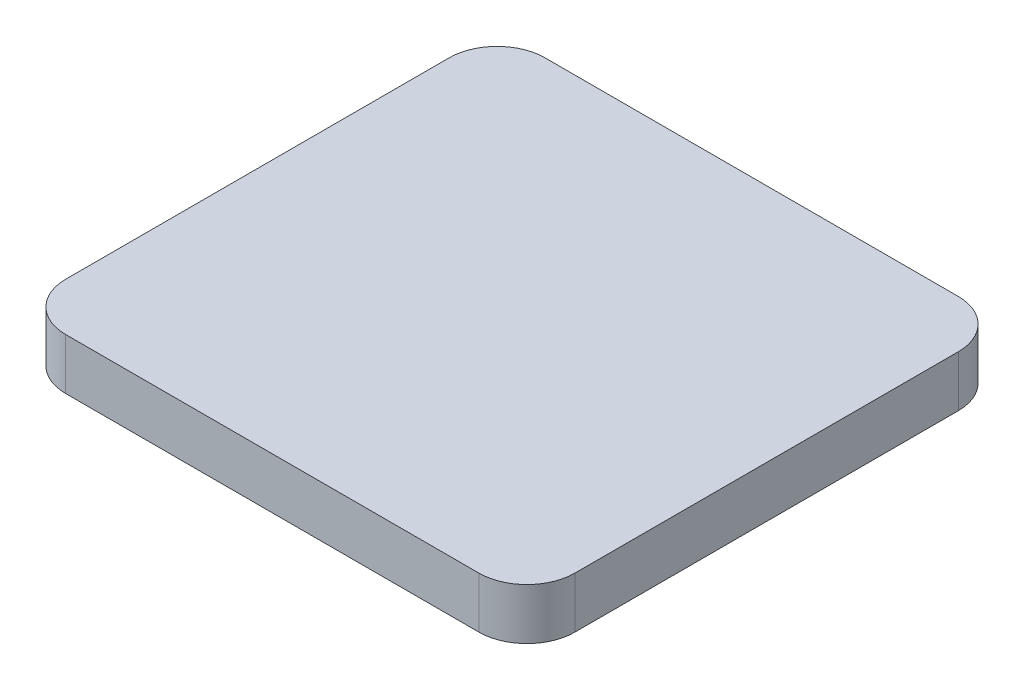
SolidWorks part; units mm, degrees
ref_plane "Front Plane" through (0, 0, 0) normal (0, 0, 1) x (1, 0, 0)
ref_plane "Top Plane" through (0, 0, 0) normal (0, 1, 0) x (1, 0, 0)
ref_plane "Right Plane" through (0, 0, 0) normal (1, 0, 0) x (0, 0, -1)
sketch "Sketch1" plane through (0, 0, 0) normal (0, 1, 0) x (1, 0, 0)
  line L0 (-21.9, 20.5) -> (-21.9, 22.5) construction
  line L1 (19.4, 20.5) -> (-19.4, 20.5)
  line L2 (21.9, 18) -> (21.9, -18)
  line L3 (19.4, -20.5) -> (-19.4, -20.5)
  line L4 (-21.9, 18) -> (-21.9, -18)
  line L5 (21.9, 20.5) -> (-21.9, -20.5) construction
  line L6 (21.9, -20.5) -> (-21.9, 20.5) construction
  line L7 (23.9, -22.5) -> (-23.9, -22.5)
  line L8 (23.9, -22.5) -> (23.9, 22.5)
  line L9 (23.9, 22.5) -> (-23.9, 22.5)
  line L10 (-23.9, -22.5) -> (-23.9, 22.5)
  line L11 (23.9, -22.5) -> (-23.9, 22.5) construction
  line L12 (23.9, 22.5) -> (-23.9, -22.5) construction
  line L13 (-21.9, 20.5) -> (-23.9, 20.5) construction
  arc A0 (-19.4, -20.5) -> (-21.9, -18) centre (-19.4, -18) cw
  arc A1 (21.9, -18) -> (19.4, -20.5) centre (19.4, -18) cw
  arc A2 (19.4, 20.5) -> (21.9, 18) centre (19.4, 18) cw
  arc A3 (-19.4, 20.5) -> (-21.9, 18) centre (-19.4, 18) ccw
  circle A4 centre (-19.4, 18) radius 4.5
  circle A5 centre (19.4, 18) radius 4.5
  circle A6 centre (19.4, -18) radius 4.5
  circle A7 centre (-19.4, -18) radius 4.5
  point P0 (0, 0)
  point P6 (0, 0)
  dimension "D4" = 2.5
  dimension "D1" = 43.8
  dimension "D2" = 41
  dimension "D3" = 2
extrude "Boss-Extrude1" add sketch "Sketch1" along normal blind 1.3 contours L1 A4 L4 A3 | A7 L4 A4 L10 | A7 L3 A0 L4 | A7 L7 A6 L3 | A6 L2 A1 L3 | A6 L8 A5 L2 | L2 A5 L1 A2 | A5 L9 A4 L1 region at (17.5292, 0, -20.6166) region at (0, 0, -21.5286) region at (-17.5292, 0, -20.6166) region at (22.9312, 0, 0) region at (23.2658, 0, 15.9336) region at (-22.9312, 0, 0) region at (0, 0, 21.5286) region at (-22.0166, 0, 16.1292)
sketch "Sketch2" plane through (0, 1.3, 0) normal (0, 1, 0) x (1, 0, 0)
  line L4 (-19.4, -22.5) -> (19.4, -22.5)
  line L5 (23.9, -18) -> (23.9, 18)
  line L6 (19.4, 22.5) -> (-19.4, 22.5)
  line L7 (-23.9, 18) -> (-23.9, -18)
  line L8 (-19.4, -22.5) -> (19.4, -22.5)
  line L9 (23.9, -18) -> (23.9, 18)
  line L10 (19.4, 22.5) -> (-19.4, 22.5)
  line L11 (-23.9, 18) -> (-23.9, -18)
  arc A4 (19.4, -22.5) -> (23.9, -18) centre (19.4, -18) ccw
  arc A5 (23.9, 18) -> (19.4, 22.5) centre (19.4, 18) ccw
  arc A6 (-19.4, 22.5) -> (-23.9, 18) centre (-19.4, 18) ccw
  arc A7 (-23.9, -18) -> (-19.4, -22.5) centre (-19.4, -18) ccw
  arc A8 (19.4, -22.5) -> (23.9, -18) centre (19.4, -18) ccw
  arc A9 (23.9, 18) -> (19.4, 22.5) centre (19.4, 18) ccw
  arc A10 (-19.4, 22.5) -> (-23.9, 18) centre (-19.4, 18) ccw
  arc A11 (-23.9, -18) -> (-19.4, -22.5) centre (-19.4, -18) ccw
  dimension "D1" = 0
extrude "Boss-Extrude2" add sketch "Sketch2" along normal blind 1.5
sketch "Sketch3" plane through (0, 1.3, 0) normal (0, -1, 0) x (1, 0, 0)
  line L0 (-23.9, 0) -> (23.9, 0) construction
  line L1 (-23.9, 18) -> (-23.9, -18) construction
  line L2 (23.9, 18) -> (23.9, -18) construction
  line L3 (-23.9, 11.25) -> (23.9, 11.25) construction
  line L4 (0, 11.25) -> (0, 22.5) construction
  line L5 (19.4, 22.5) -> (-19.4, 22.5) construction
  line L6 (0, 11.25) -> (0, 0) construction
  line L7 (-23.9, -11.25) -> (23.9, -11.25) construction
  line L8 (0, 0) -> (4.1348, 4.1348) construction
  line L9 (11.25, -23.9) -> (11.25, 23.9) construction
  line L10 (-11.25, -23.9) -> (-11.25, 23.9) construction
  line L11 (-21.9, -18) -> (-21.9, 18) construction
  line L12 (-21.9, -18) -> (-21.9, 18) construction
  line L13 (19.4, -20.5) -> (-19.4, -20.5) construction
  line L14 (21.9, -18) -> (21.9, 18) construction
  line L15 (19.4, 20.5) -> (-19.4, 20.5) construction
  line L16 (19.4, 20.5) -> (-19.4, 20.5) construction
  circle A0 centre (-21.9, 11.25) radius 0.4
  circle A1 centre (-21.9, 0) radius 0.4
  circle A2 centre (-21.9, -11.25) radius 0.4
  circle A3 centre (-11.25, -20.5) radius 0.4
  circle A4 centre (11.25, -20.5) radius 0.4
  circle A5 centre (21.9, -11.25) radius 0.4
  circle A6 centre (21.9, 0) radius 0.4
  circle A7 centre (21.9, 11.25) radius 0.4
  circle A8 centre (11.25, 20.5) radius 0.4
  circle A9 centre (0, 20.5) radius 0.4
  circle A10 centre (-11.25, 20.5) radius 0.4
  point P56 (-21.6, 0)
  point P57 (21.6, -10.85)
  dimension "D2" = 0.8
  dimension "D1" = 45
extrude "Boss-Extrude3" add sketch "Sketch3" along normal up to surface (1.3 mm away) up to face at (0, 0, 0)
sketch "Sketch4" plane through (0, 0, 0) normal (0, -1, 0) x (1, 0, 0)
  line L0 (-22.9, 18) -> (-22.9, -18)
  line L1 (-19.4, -21.5) -> (19.4, -21.5)
  line L2 (22.9, -18) -> (22.9, 18)
  line L3 (19.4, 21.5) -> (-19.4, 21.5)
  line L4 (19.4, 22.5) -> (-19.4, 22.5)
  line L5 (-23.9, 18) -> (-23.9, -18)
  line L6 (-19.4, -22.5) -> (19.4, -22.5)
  line L7 (23.9, -18) -> (23.9, 18)
  line L8 (19.4, 22.5) -> (-19.4, 22.5)
  line L9 (-23.9, 18) -> (-23.9, -18)
  line L10 (-19.4, -22.5) -> (19.4, -22.5)
  line L11 (23.9, -18) -> (23.9, 18)
  arc A0 (-19.4, 21.5) -> (-22.9, 18) centre (-19.4, 18) ccw
  arc A1 (-22.9, -18) -> (-19.4, -21.5) centre (-19.4, -18) ccw
  arc A2 (19.4, -21.5) -> (22.9, -18) centre (19.4, -18) ccw
  arc A3 (22.9, 18) -> (19.4, 21.5) centre (19.4, 18) ccw
  arc A4 (-19.4, 22.5) -> (-23.9, 18) centre (-19.4, 18) ccw
  arc A5 (-23.9, -18) -> (-19.4, -22.5) centre (-19.4, -18) ccw
  arc A6 (19.4, -22.5) -> (23.9, -18) centre (19.4, -18) ccw
  arc A7 (23.9, 18) -> (19.4, 22.5) centre (19.4, 18) ccw
  arc A8 (-19.4, 22.5) -> (-23.9, 18) centre (-19.4, 18) ccw
  arc A9 (-23.9, -18) -> (-19.4, -22.5) centre (-19.4, -18) ccw
  arc A10 (19.4, -22.5) -> (23.9, -18) centre (19.4, -18) ccw
  arc A11 (23.9, 18) -> (19.4, 22.5) centre (19.4, 18) ccw
  dimension "D1" = 0
  dimension "D2" = 1
extrude "Boss-Extrude4" add sketch "Sketch4" along normal blind 2
sketch "Sketch5" plane through (0, 1.3, 0) normal (0, -1, 0) x (1, 0, 0)
  line L31 (-12.2298, 19.5) -> (-19.4, 19.5)
  line L32 (-20.9, 18) -> (-20.9, 12.2298)
  line L33 (-20.9, 10.2702) -> (-20.9, 0.9798)
  line L34 (-20.9, -0.9798) -> (-20.9, -10.2702)
  line L35 (-20.9, -12.2298) -> (-20.9, -18)
  line L36 (-19.4, -19.5) -> (-12.2298, -19.5)
  line L37 (-10.2702, -19.5) -> (10.2702, -19.5)
  line L38 (12.2298, -19.5) -> (19.4, -19.5)
  line L39 (20.9, -18) -> (20.9, -12.2298)
  line L40 (20.9, -10.2702) -> (20.9, -0.9798)
  line L41 (20.9, 0.9798) -> (20.9, 10.2702)
  line L42 (20.9, 12.2298) -> (20.9, 18)
  line L43 (19.4, 19.5) -> (12.2298, 19.5)
  line L44 (10.2702, 19.5) -> (0.9798, 19.5)
  line L45 (-0.9798, 19.5) -> (-10.2702, 19.5)
  line L46 (-12.2298, 19.5) -> (-19.4, 19.5)
  line L47 (-20.9, 18) -> (-20.9, 12.2298)
  line L48 (-20.9, 10.2702) -> (-20.9, 0.9798)
  line L49 (-20.9, -0.9798) -> (-20.9, -10.2702)
  line L50 (-20.9, -12.2298) -> (-20.9, -18)
  line L51 (-19.4, -19.5) -> (-12.2298, -19.5)
  line L52 (-10.2702, -19.5) -> (10.2702, -19.5)
  line L53 (12.2298, -19.5) -> (19.4, -19.5)
  line L54 (20.9, -18) -> (20.9, -12.2298)
  line L55 (20.9, -10.2702) -> (20.9, -0.9798)
  line L56 (20.9, 0.9798) -> (20.9, 10.2702)
  line L57 (20.9, 12.2298) -> (20.9, 18)
  line L58 (19.4, 19.5) -> (12.2298, 19.5)
  line L59 (10.2702, 19.5) -> (0.9798, 19.5)
  line L60 (-0.9798, 19.5) -> (-10.2702, 19.5)
  arc A30 (-12.2298, 19.5) -> (-10.2702, 19.5) centre (-11.25, 20.5) ccw
  arc A31 (-19.4, 19.5) -> (-20.9, 18) centre (-19.4, 18) ccw
  arc A32 (-20.9, 10.2702) -> (-20.9, 12.2298) centre (-21.9, 11.25) ccw
  arc A33 (-20.9, -0.9798) -> (-20.9, 0.9798) centre (-21.9, 0) ccw
  arc A34 (-20.9, -12.2298) -> (-20.9, -10.2702) centre (-21.9, -11.25) ccw
  arc A35 (-20.9, -18) -> (-19.4, -19.5) centre (-19.4, -18) ccw
  arc A36 (-10.2702, -19.5) -> (-12.2298, -19.5) centre (-11.25, -20.5) ccw
  arc A37 (12.2298, -19.5) -> (10.2702, -19.5) centre (11.25, -20.5) ccw
  arc A38 (19.4, -19.5) -> (20.9, -18) centre (19.4, -18) ccw
  arc A39 (20.9, -10.2702) -> (20.9, -12.2298) centre (21.9, -11.25) ccw
  arc A40 (20.9, 0.9798) -> (20.9, -0.9798) centre (21.9, 0) ccw
  arc A41 (20.9, 12.2298) -> (20.9, 10.2702) centre (21.9, 11.25) ccw
  arc A42 (20.9, 18) -> (19.4, 19.5) centre (19.4, 18) ccw
  arc A43 (10.2702, 19.5) -> (12.2298, 19.5) centre (11.25, 20.5) ccw
  arc A44 (-0.9798, 19.5) -> (0.9798, 19.5) centre (0, 20.5) ccw
  arc A45 (-12.2298, 19.5) -> (-10.2702, 19.5) centre (-11.25, 20.5) ccw
  arc A46 (-19.4, 19.5) -> (-20.9, 18) centre (-19.4, 18) ccw
  arc A47 (-20.9, 10.2702) -> (-20.9, 12.2298) centre (-21.9, 11.25) ccw
  arc A48 (-20.9, -0.9798) -> (-20.9, 0.9798) centre (-21.9, 0) ccw
  arc A49 (-20.9, -12.2298) -> (-20.9, -10.2702) centre (-21.9, -11.25) ccw
  arc A50 (-20.9, -18) -> (-19.4, -19.5) centre (-19.4, -18) ccw
  arc A51 (-10.2702, -19.5) -> (-12.2298, -19.5) centre (-11.25, -20.5) ccw
  arc A52 (12.2298, -19.5) -> (10.2702, -19.5) centre (11.25, -20.5) ccw
  arc A53 (19.4, -19.5) -> (20.9, -18) centre (19.4, -18) ccw
  arc A54 (20.9, -10.2702) -> (20.9, -12.2298) centre (21.9, -11.25) ccw
  arc A55 (20.9, 0.9798) -> (20.9, -0.9798) centre (21.9, 0) ccw
  arc A56 (20.9, 12.2298) -> (20.9, 10.2702) centre (21.9, 11.25) ccw
  arc A57 (20.9, 18) -> (19.4, 19.5) centre (19.4, 18) ccw
  arc A58 (10.2702, 19.5) -> (12.2298, 19.5) centre (11.25, 20.5) ccw
  arc A59 (-0.9798, 19.5) -> (0.9798, 19.5) centre (0, 20.5) ccw
  dimension "D1" = 1
extrude "Cut-Extrude1" cut sketch "Sketch5" against normal blind 0.5
